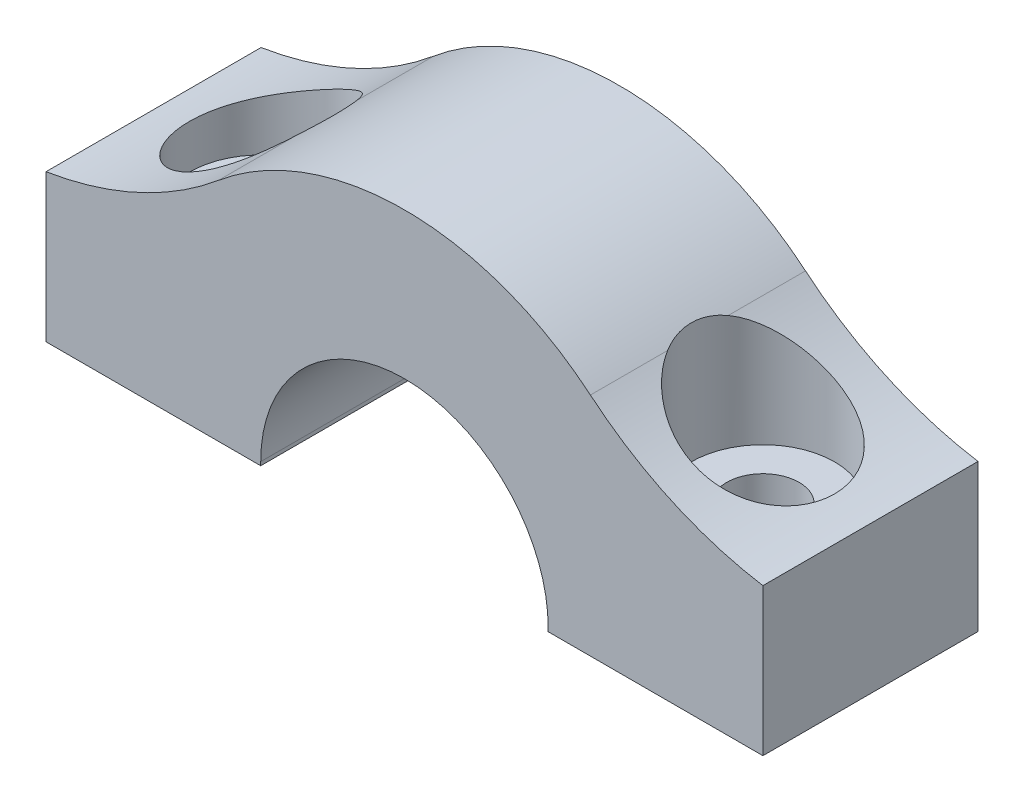
SolidWorks part; units mm, degrees
material "ABS"
ref_plane "Front Plane" through (0, 0, 0) normal (0, 0, 1) x (1, 0, 0)
ref_plane "Top Plane" through (0, 0, 0) normal (0, 1, 0) x (1, 0, 0)
ref_plane "Right Plane" through (0, 0, 0) normal (1, 0, 0) x (0, 0, -1)
sketch "Sketch1" plane through (0, 0, 0) normal (0, 1, 0) x (1, 0, 0)
  line L1 (0, 0) -> (20, 0)
  line L2 (0, 0) -> (0, 6)
  line L3 (0, 6) -> (20, 6)
  line L4 (20, 0) -> (20, 6)
extrude "Boss-Extrude1" add sketch "Sketch1" along normal blind 4.01
sketch "Sketch2" plane through (0, 0, 0) normal (0, 0, 1) x (1, 0, 0)
  line L0 (0, 0) -> (20, 0) construction
  line L1 (2.9738, 4.01) -> (17.0262, 4.01)
  line L2 (0, 4.01) -> (20, 4.01) construction
  arc A1 (17.0262, 4.01) -> (2.9738, 4.01) centre (10, 0) ccw
extrude "Boss-Extrude2" add sketch "Sketch2" against normal blind 6
sketch "Sketch5" plane through (0, 0, 0) normal (0, -1, 0) x (1, 0, 0)
  line L1 (0, 0) -> (20, 0)
  line L2 (0, 0) -> (0, -6)
  line L3 (0, -6) -> (20, -6)
  line L4 (20, 0) -> (20, -6)
extrude "Boss-Extrude3" add sketch "Sketch5" along normal blind 3
sketch "Sketch6" plane through (0, 0, 0) normal (0, 0, 1) x (1, 0, 0)
  line L0 (0, 4.01) -> (2.9738, 4.01) construction
  line L1 (0, 4.01) -> (0, -3) construction
  circle A0 centre (10, 0) radius 4.01
  dimension "D1" = 4.01
  dimension "D2" = 10
extrude "Cut-Extrude2" cut sketch "Sketch6" against normal blind 8
sketch "Sketch7" plane through (0, -3, 0) normal (0, -1, 0) x (1, 0, 0)
  line L1 (0, 0) -> (20, 0)
  line L2 (0, 0) -> (0, -6)
  line L3 (0, -6) -> (20, -6)
  line L4 (20, 0) -> (20, -6)
extrude "Cut-Extrude3" cut sketch "Sketch7" against normal blind 3
fillet "Fillet1" radius 10 2 edges at (17.0262, 4.01, -3) (2.9738, 4.01, -3)
sketch "Sketch8" plane through (0, 0, 0) normal (0, -1, 0) x (1, 0, 0)
  line L0 (5.99, 0) -> (0, 0) construction
  line L1 (0, 0) -> (0, -6) construction
  line L2 (10, 0) -> (10, -6) construction
  line L3 (14.01, 0) -> (5.99, 0) construction
  line L4 (5.99, -6) -> (14.01, -6) construction
  circle A0 centre (3, -3) radius 1.01
  circle A1 centre (17, -3) radius 1.01
  dimension "D1" = 3
  dimension "D2" = 3
extrude "Cut-Extrude4" cut sketch "Sketch8" against normal through all
sketch "Sketch9" plane through (0, 0, 0) normal (0, -1, 0) x (1, 0, 0)
  circle A0 centre (3, -3) radius 2
  circle A1 centre (17, -3) radius 2
extrude "Cut-Extrude5" cut sketch "Sketch9" against normal blind 10 from offset 3 offset against normal yes
sketch "Sketch10" plane through (0, 0, 0) normal (0, -1, 0) x (1, 0, 0)
  line L1 (0, 0) -> (5.99, 0)
  line L2 (0, 0) -> (0, -6)
  line L3 (0, -6) -> (5.99, -6)
  line L4 (5.99, 0) -> (5.99, -6)
  line L5 (14.01, 0) -> (20, 0)
  line L6 (14.01, 0) -> (14.01, -6)
  line L7 (14.01, -6) -> (20, -6)
  line L8 (20, 0) -> (20, -6)
  circle A0 centre (3, -3) radius 1.01
  circle A1 centre (17, -3) radius 1.01
extrude "Boss-Extrude4" add sketch "Sketch10" along normal blind 0.1
